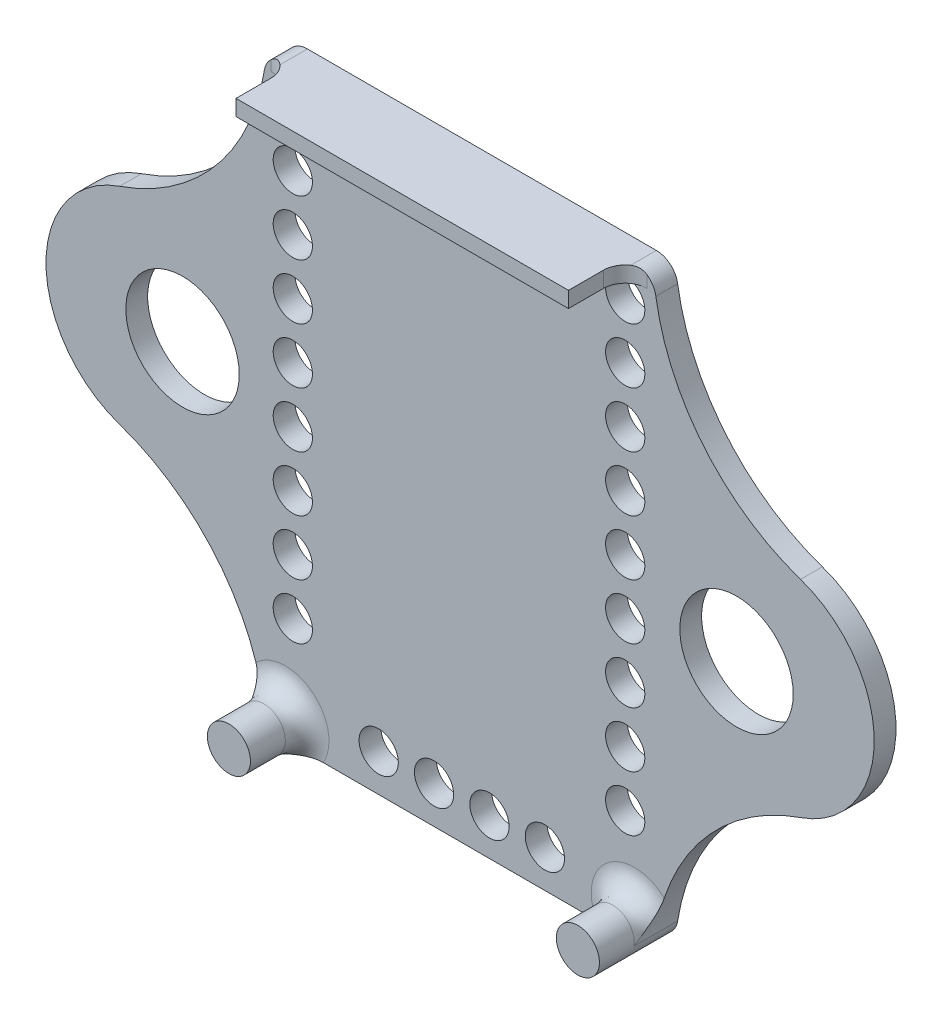
SolidWorks part; units mm, degrees
ref_plane "Front Plane" through (0, 0, 0) normal (0, 0, 1) x (1, 0, 0)
ref_plane "Top Plane" through (0, 0, 0) normal (0, 1, 0) x (1, 0, 0)
ref_plane "Right Plane" through (0, 0, 0) normal (1, 0, 0) x (0, 0, -1)
sketch "Sketch1" plane through (0, 0, 0) normal (0, 0, 1) x (1, 0, 0)
  line L0 (-35.001, -25.4128) -> (-19.001, -25.4128)
  line L1 (-18.0137, -26.4001) -> (-18.0137, -51.4001)
  line L2 (-19.001, -52.3874) -> (-35.001, -52.3874)
  line L3 (-35.9884, -51.4001) -> (-35.9884, -26.4001)
  line L4 (-35.9884, -38.9001) -> (-40.9884, -38.9001)
  line L5 (-18.0137, -38.9001) -> (-13.0137, -38.9001)
  line L6 (-40.9884, -33.9001) -> (-35.9884, -33.9001)
  line L7 (-40.9884, -43.9001) -> (-35.9884, -43.9001)
  line L8 (-13.0137, -43.9001) -> (-18.0137, -43.9001)
  line L9 (-13.0137, -33.9001) -> (-18.0137, -33.9001)
  circle A0 centre (-34.671, -27.0511) radius 0.5
  circle A1 centre (-34.671, -29.5911) radius 0.5
  circle A2 centre (-34.671, -32.1311) radius 0.5
  circle A3 centre (-34.671, -34.6711) radius 0.5
  circle A4 centre (-34.671, -37.2111) radius 0.5
  circle A5 centre (-34.671, -39.7511) radius 0.5
  circle A6 centre (-34.671, -42.2911) radius 0.5
  circle A7 centre (-34.671, -44.8311) radius 0.5
  circle A8 centre (-34.671, -47.3711) radius 0.5
  circle A9 centre (-30.7341, -50.6731) radius 0.55
  circle A10 centre (-28.1941, -50.6731) radius 0.55
  circle A11 centre (-25.6541, -50.6731) radius 0.55
  circle A12 centre (-23.114, -50.6731) radius 0.55
  circle A13 centre (-19.4311, -47.3711) radius 0.5
  circle A14 centre (-19.4311, -44.8311) radius 0.5
  circle A15 centre (-19.4311, -42.2911) radius 0.5
  circle A16 centre (-19.4311, -39.7511) radius 0.5
  circle A17 centre (-19.4311, -37.2111) radius 0.5
  circle A18 centre (-19.4311, -34.6711) radius 0.5
  circle A19 centre (-19.4311, -32.1311) radius 0.5
  circle A20 centre (-19.4311, -29.5911) radius 0.5
  circle A21 centre (-19.4311, -27.0511) radius 0.5
  circle A22 centre (-35.001, -26.4001) radius 0.9873
  circle A23 centre (-19.001, -26.4001) radius 0.9873
  circle A24 centre (-35.001, -51.4001) radius 0.9873
  circle A25 centre (-19.001, -51.4001) radius 0.9873
  circle A28 centre (-34.671, -27.0511) radius 0.9
  circle A29 centre (-34.671, -29.5911) radius 0.9
  circle A30 centre (-34.671, -32.1311) radius 0.9
  circle A31 centre (-34.671, -34.6711) radius 0.9
  circle A32 centre (-34.671, -37.2111) radius 0.9
  circle A33 centre (-34.671, -39.7511) radius 0.9
  circle A34 centre (-34.671, -42.2911) radius 0.9
  circle A35 centre (-34.671, -44.8311) radius 0.9
  circle A36 centre (-34.671, -47.3711) radius 0.9
  circle A37 centre (-30.7341, -50.6731) radius 0.9
  circle A38 centre (-28.1941, -50.6731) radius 0.9
  circle A39 centre (-25.6541, -50.6731) radius 0.9
  circle A40 centre (-23.114, -50.6731) radius 0.9
  circle A41 centre (-19.4311, -47.3711) radius 0.9
  circle A42 centre (-19.4311, -44.8311) radius 0.9
  circle A43 centre (-19.4311, -42.2911) radius 0.9
  circle A44 centre (-19.4311, -39.7511) radius 0.9
  circle A45 centre (-19.4311, -37.2111) radius 0.9
  circle A46 centre (-19.4311, -34.6711) radius 0.9
  circle A47 centre (-19.4311, -32.1311) radius 0.9
  circle A48 centre (-19.4311, -29.5911) radius 0.9
  circle A49 centre (-19.4311, -27.0511) radius 0.9
  circle A50 centre (-40.9884, -38.9001) radius 1.7
  circle A51 centre (-13.0137, -38.9001) radius 1.7
  circle A52 centre (-40.9884, -38.9001) radius 5
  circle A53 centre (-13.0137, -38.9001) radius 5
extrude "Boss-Extrude1" add sketch "Sketch1" along normal blind 1 contours A52 A50 | A53 A51 | A52 L7 L3 | A49 A23 L0 A22 A28 L3 A24 L2 A25 L1 A48 A47 A46 A45 A44 A43 A42 A41 A40 A39 A38 A37 A36 A35 A34 A33 | A53 L1 L8 | A53 L9 L1 | A52 L3 L6 | A28 A22 | A49 A23 | A25 | A24 | A50 | A51 region at (-26.9992, -38.717, 0) region at (-35.1699, -26.067, 0) region at (-18.8063, -26.1053, 0) region at (-37.1052, -35.0169, 0) region at (-16.8969, -35.0169, 0) region at (-42.6403, -38.9001, 0) region at (-37.5528, -42.3356, 0) region at (-37.1052, -42.7832, 0) region at (-16.8969, -42.7832, 0) region at (-13.0137, -37.2482, 0) region at (-16.4492, -35.4645, 0) region at (-35.001, -51.4001, 0) region at (-19.001, -51.4001, 0)
fillet "Fillet1" radius 10 4 edges at (-35.9884, -43.9001, 0.5) (-35.9884, -33.9001, 0.5) (-18.0137, -33.9001, 0.5) (-18.0137, -43.9001, 0.5)
sketch "Sketch2" plane through (0, 0, 1) normal (0, 0, 1) x (1, 0, 0)
  line L0 (-27.001, -25.4128) -> (-27.001, -26.1371)
  line L1 (-35.001, -25.4128) -> (-19.001, -25.4128) construction
  line L2 (-27.001, -26.1371) -> (-19.4311, -26.1371)
  line L3 (-19.4311, -26.1371) -> (-19.4311, -25.4128)
  line L4 (-27.001, -26.1371) -> (-34.6754, -26.1371)
  line L5 (-34.6754, -26.1371) -> (-34.6754, -25.4128)
  line L6 (-34.6754, -25.4128) -> (-19.4311, -25.4128)
  circle A0 centre (-35.001, -51.4001) radius 0.9873
  circle A1 centre (-19.001, -51.4001) radius 0.9873
  arc M6 (-35.9766, -51.5517) -> (-35.001, -52.3874) centre (-35.001, -51.4001) ccw
  arc M8 (-19.001, -52.3874) -> (-18.0254, -51.5517) centre (-19.001, -51.4001) ccw
  line M13 (-19.001, -25.4128) -> (-35.001, -25.4128)
extrude "Boss-Extrude2" add sketch "Sketch2" along normal blind 2.6 contours A1 M8 | A0 M6 | L2 L3 L0 M13 | L5 L4 L0 M13 region at (-23.216, -25.7749, 1) region at (-30.8382, -25.7749, 1) region at (-35.001, -51.4001, 1) region at (-19.001, -51.4001, 1)
fillet "Fillet2" radius 1 2 edges at (-19.4311, -25.7749, 1) (-34.6754, -25.7749, 1)
fillet "Fillet3" radius 1 2 edges at (-19.6433, -50.6503, 1) (-34.3588, -50.6503, 1)
sketch "Sketch3" plane through (0, 0, 1) normal (0, 0, 1) x (1, 0, 0)
  line L0 (-27.0532, -25.4128) -> (-27.001, -52.3874)
  line L1 (-19.4311, -25.4128) -> (-34.6754, -25.4128) construction
  line L2 (-20.7257, -52.3874) -> (-33.2763, -52.3874) construction
  line L3 (-27.0271, -38.9001) -> (-14.3271, -38.9001)
  line L4 (-27.0271, -38.9001) -> (-39.7271, -38.9001)
  circle A0 centre (-39.7271, -38.9001) radius 2.6
  circle A1 centre (-14.3271, -38.9001) radius 2.6
extrude "Cut-Extrude1" cut sketch "Sketch3" against normal up to surface (1 mm away) contours A1 | A0 region at (-14.3271, -36.3736, 1) region at (-42.2536, -38.9001, 1) up to face at (-27.001, -38.9001, 0)
